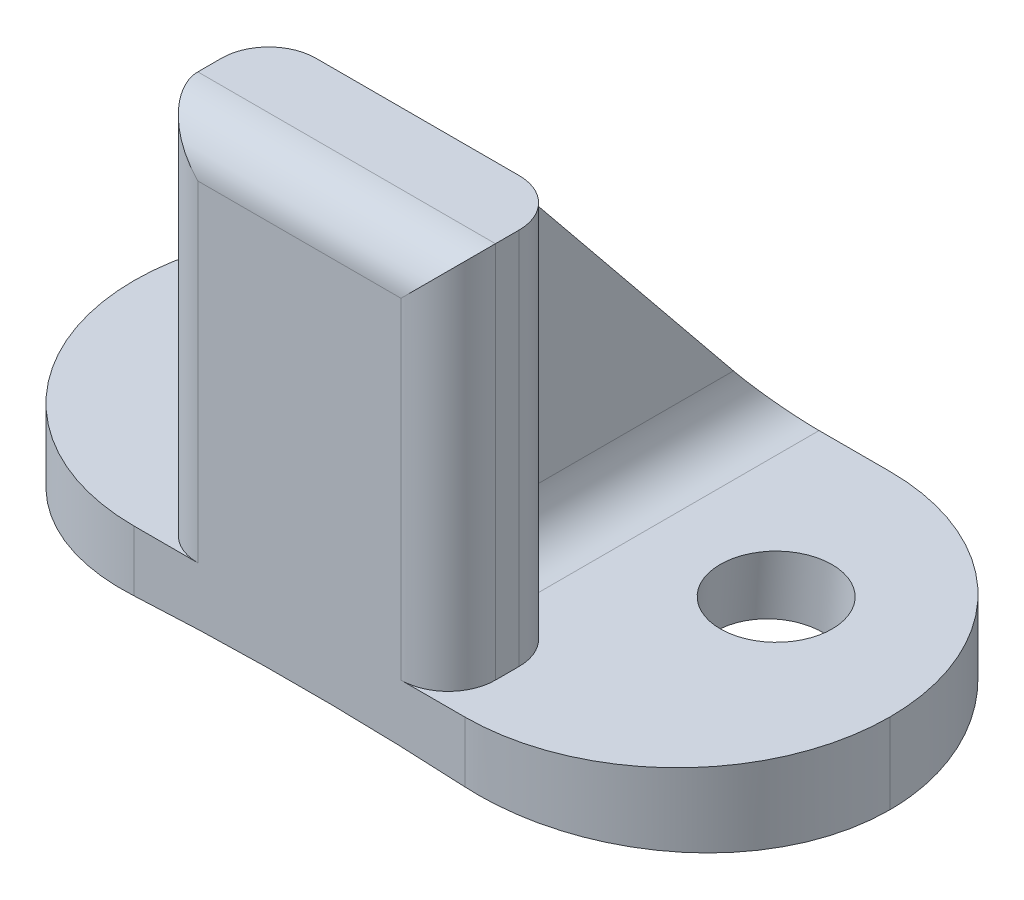
SolidWorks part; units mm, degrees
ref_plane "Front Plane" through (0, 0, 0) normal (0, 0, 1) x (1, 0, 0)
ref_plane "Top Plane" through (0, 0, 0) normal (0, 1, 0) x (1, 0, 0)
ref_plane "Right Plane" through (0, 0, 0) normal (1, 0, 0) x (0, 0, -1)
sketch "Sketch1" plane through (0, 0, 0) normal (0, 1, 0) x (1, 0, 0)
  line L0 (6, -10.985) -> (7, -10.985)
  line L1 (-10.16, 4.445) -> (10.16, 4.445)
  line L2 (-10.16, 4.445) -> (-10.16, -19.3675)
  line L3 (-10.16, -19.3675) -> (10.16, -19.3675)
  line L4 (10.16, 4.445) -> (10.16, -19.3675)
  line L5 (-6, -6.985) -> (6, -6.985)
  line L6 (-6, -6.985) -> (-6, -13.985)
  line L7 (-6, -13.985) -> (6, -13.985)
  line L8 (6, -6.985) -> (6, -13.985)
  line L9 (7, -10.985) -> (7, -4.445)
  line L10 (7, -4.445) -> (-7, -4.445)
  line L11 (-7, -4.445) -> (-7, -10.985)
  line L12 (-7, -10.985) -> (-6, -10.985)
  line L13 (6, -10.985) -> (3.9, -10.985)
  line L14 (3.9, -10.985) -> (3.9, -9.985)
  line L15 (3.9, -9.985) -> (6, -9.985)
  line L16 (-6, -10.985) -> (-3.9, -10.985)
  line L17 (-3.9, -10.985) -> (-3.9, -9.985)
  line L18 (-3.9, -9.985) -> (-6, -9.985)
  line L19 (-3.9, -9.985) -> (-3.9, -6.985)
  line L20 (3.9, -9.985) -> (3.9, -6.985)
  line L21 (0, -7.3881) -> (0, 0) construction
  line L22 (-3, -13.985) -> (-3, -17.16)
  line L23 (-3, -17.16) -> (3, -17.16)
  line L24 (3, -17.16) -> (3, -13.985)
  point P23 (0, -19.3675)
  point P24 (0, -17.16)
  point P27 (0, -6.985)
  dimension "D1" = 12
  dimension "D2" = 7
  dimension "D3" = 1
  dimension "D4" = 2.54
  dimension "D5" = 7.8
  dimension "D6" = 3
  dimension "D7" = 1
  dimension "D8" = 6.985
  dimension "D9" = 23.8125
  dimension "D10" = 20.32
  dimension "D11" = 4.445
  dimension "D12" = 3.175
  dimension "D13" = 6
sketch "Sketch2" plane through (0, 0, 0) normal (0, 0, 1) x (1, 0, 0)
  line L0 (0, 0) -> (0, -76.859) construction
  circle A0 centre (0, -76.859) radius 78.359
  dimension "D1" = 156.718
  dimension "D2" = 76.859
ref_axis "Axis1" through (0, -76.859, 0) along (0, 0, 1)
ref_plane "Plane1" through (-5.5819, -76.4515, 0) normal (0.0728, 0.9973, 0) x (0, 0, 1)
sketch "Sketch3" plane through (-5.5819, -76.4515, 0) normal (0.0728, 0.9973, 0) x (0, 0, 1)
  line L0 (0, -72.7623) -> (0, 83.9557) construction
  circle A0 centre (0, 5.5967) radius 1.5
  dimension "D1" = 3
extrude "Boss-Extrude1" add sketch "Sketch1" along normal blind 3 contours L3 L21 L7 L6 L12 L11 L10 L1 L2 | L21 L3 L4 L1 L10 L9 L0 L8 L7 | L5 L21 L10 L11 L12 L6 | L21 L5 L8 L0 L9 L10 | L20 L15 L8 L5 | L18 L19 L5 L6 | L15 L14 L13 L8 | L17 L18 L6 L16 region at (4.051, 0, 6.3156) region at (4.95, 0, 10.485) region at (4.95, 0, 8.485) region at (-4.051, 0, 6.3156) region at (-4.95, 0, 8.485) region at (-4.95, 0, 10.485) region at (0, 0, -4.132)
extrude "Cut-Extrude1" cut sketch "Sketch3" along normal through all contours A0
mirror "Mirror1" about plane through (0, 0, 0) normal (1, 0, 0) of "Cut-Extrude1"
extrude "Cut-Extrude2" cut sketch "Sketch2" against normal through all both and the other way through all
sketch "Sketch4" plane through (0, 0, 19.3675) normal (0, 0, 1) x (1, 0, 0)
  line L1 (-12.7, 21.1446) -> (10.16, 21.1446)
  line L2 (-12.7, 21.1446) -> (-12.7, 0.8385)
  line L3 (-12.7, 0.8385) -> (10.16, 0.8385)
  line L4 (10.16, 21.1446) -> (10.16, 0.8385)
extrude "Cut-Extrude3" cut sketch "Sketch4" against normal up to surface (12.3825 mm away) up to face at (0, 2.2257, 6.985)
sketch "Sketch9" plane through (0, 3, 0) normal (0, 1, 0) x (1, 0, 0)
  line L0 (-10.16, -6.985) -> (10.16, -6.985) construction
  line L1 (4, -6.985) -> (-4, -6.985)
  line L2 (4, -6.985) -> (4, -3.81)
  line L3 (4, -3.81) -> (-4, -3.81)
  line L4 (-4, -6.985) -> (-4, -3.81)
  point P6 (0, -3.81)
  dimension "D1" = 8
  dimension "D2" = 3.175
extrude "Boss-Extrude2" add sketch "Sketch9" along normal blind 10.16
sketch "Sketch10" plane through (0, 0, 0) normal (1, 0, 0) x (0, 0, -1)
  line L0 (-3.81, 13.16) -> (4.445, 3)
  line L1 (4.445, 3) -> (-3.81, 3)
  line L2 (-3.81, 3) -> (-3.81, 13.16)
extrude "Boss-Extrude3" add sketch "Sketch10" along normal mid plane 2.54
fillet "Fillet7" radius 5.715 4 edges at (-10.16, 1.9193, 6.985) (-10.16, 1.9193, -4.445) (10.16, 1.9193, -4.445) (10.16, 1.9193, 6.985)
fillet "Fillet8" radius 1.27 5 edges at (4, 8.08, 3.81) (-4, 8.08, 3.81) (0, 13.16, 6.985) (4, 8.08, 6.985) (-4, 8.08, 6.985)
fillet "Fillet9" radius 1.27 4 edges at (-1.27, 3, -0.3175) (-1.27, 8.08, 3.81) (1.27, 3, -0.3175) (1.27, 8.08, 3.81)
equation "\"D2@Sketch2\"=(6.17/2)*1in - 1.5mm"
equation "\"D1@Sketch3\"=3mm"
